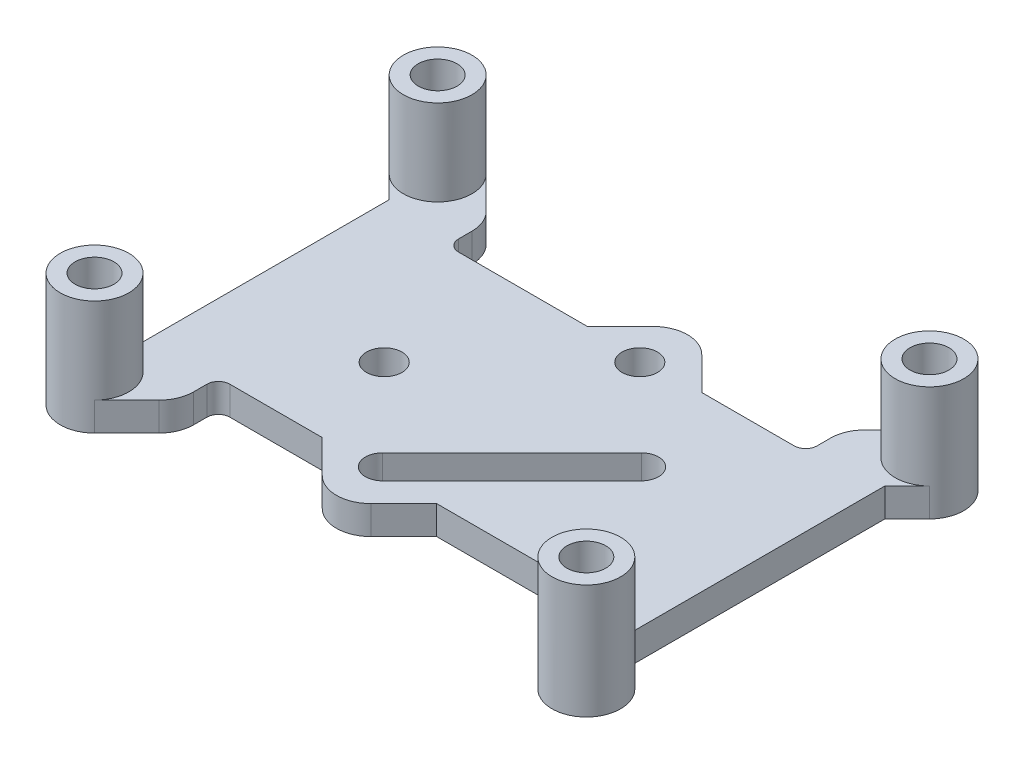
SolidWorks part; units mm, degrees
ref_plane "Front Plane" through (0, 0, 0) normal (0, 0, 1) x (1, 0, 0)
ref_plane "Top Plane" through (0, 0, 0) normal (0, 1, 0) x (1, 0, 0)
ref_plane "Right Plane" through (0, 0, 0) normal (1, 0, 0) x (0, 0, -1)
sketch "Sketch1" plane through (0, 0, 0) normal (0, 1, 0) x (1, 0, 0)
  line L1 (-21.5, 15) -> (21.5, 15) construction
  line L2 (-21.5, 15) -> (-21.5, -15) construction
  line L3 (-21.5, -15) -> (21.5, -15) construction
  line L4 (21.5, 15) -> (21.5, -15) construction
  line L5 (-21.5, 15) -> (21.5, -15) construction
  line L6 (-21.5, -15) -> (21.5, 15) construction
  circle A0 centre (-21.5, 15) radius 1.7
  circle A1 centre (21.5, 15) radius 1.7
  circle A2 centre (21.5, -15) radius 1.7
  circle A3 centre (-21.5, -15) radius 1.7
  circle A4 centre (-21.5, 15) radius 3
  circle A5 centre (-21.5, -15) radius 3
  circle A6 centre (21.5, -15) radius 3
  circle A7 centre (21.5, 15) radius 3
  point P0 (0, 0)
  dimension "D3" = 3.4
  dimension "D4" = 6
  dimension "D1" = 43
  dimension "D2" = 30
extrude "Boss-Extrude1" add sketch "Sketch1" along normal blind 10
sketch "Sketch2" plane through (0, 0, 0) normal (0, 1, 0) x (1, 0, 0)
  line L0 (-21.5, 15) -> (-18.6716, 12.1716) construction
  line L1 (-19.3787, 17.1213) -> (-16.5503, 14.2929)
  line L2 (-23.6213, 12.8787) -> (-21.6716, 10.9289)
  line L3 (-21.5, -15) -> (-18.6716, -12.1716) construction
  line L4 (-23.6213, -12.8787) -> (-21.6716, -10.9289)
  line L5 (-19.3787, -17.1213) -> (-16.5503, -14.2929)
  line L6 (-18.6716, 12.1716) -> (-18.6716, -12.1716) construction
  line L7 (-15.6716, 12.1716) -> (-15.6716, -12.1716)
  line L8 (-21.6716, 10.9289) -> (-21.6716, -10.9289)
  line L9 (0, -1000) -> (0, 49000) construction
  line L10 (18.6716, 12.1716) -> (18.6716, -12.1716) construction
  line L11 (21.5, -15) -> (18.6716, -12.1716) construction
  line L12 (21.5, 15) -> (18.6716, 12.1716) construction
  line L13 (21.6716, 10.9289) -> (21.6716, -10.9289)
  line L14 (15.6716, 12.1716) -> (15.6716, -12.1716)
  line L15 (19.3787, -17.1213) -> (16.5503, -14.2929)
  line L16 (23.6213, -12.8787) -> (21.6716, -10.9289)
  line L17 (23.6213, 12.8787) -> (21.6716, 10.9289)
  line L18 (19.3787, 17.1213) -> (16.5503, 14.2929)
  arc A0 (-19.3787, 17.1213) -> (-23.6213, 12.8787) centre (-21.5, 15) ccw
  circle A2 centre (-21.5, 15) radius 3 construction
  arc A3 (-23.6213, -12.8787) -> (-19.3787, -17.1213) centre (-21.5, -15) ccw
  arc A4 (-16.5503, -14.2929) -> (-15.6716, -12.1716) centre (-18.6716, -12.1716) ccw
  circle A5 centre (-21.5, -15) radius 3 construction
  arc A6 (-15.6716, 12.1716) -> (-16.5503, 14.2929) centre (-18.6716, 12.1716) ccw
  arc A7 (-16.5503, -14.2929) -> (-15.6716, -12.1716) centre (-18.6716, -12.1716) ccw
  arc A8 (-15.6716, 12.1716) -> (-16.5503, 14.2929) centre (-18.6716, 12.1716) ccw
  arc A9 (15.6716, 12.1716) -> (16.5503, 14.2929) centre (18.6716, 12.1716) cw
  arc A10 (16.5503, -14.2929) -> (15.6716, -12.1716) centre (18.6716, -12.1716) cw
  arc A11 (15.6716, 12.1716) -> (16.5503, 14.2929) centre (18.6716, 12.1716) cw
  arc A12 (16.5503, -14.2929) -> (15.6716, -12.1716) centre (18.6716, -12.1716) cw
  arc A13 (23.6213, -12.8787) -> (19.3787, -17.1213) centre (21.5, -15) cw
  arc A14 (19.3787, 17.1213) -> (23.6213, 12.8787) centre (21.5, 15) cw
  point P2 (-20.0858, 13.5858)
  point P13 (-20.0858, -13.5858)
  point P20 (-18.6716, 0)
  point P41 (18.6716, 0)
  point P42 (20.0858, -13.5858)
  point P43 (20.0858, 13.5858)
  dimension "D1" = 45
  dimension "D2" = 45
  dimension "D3" = 4
  dimension "D4" = 4
  dimension "D5" = 3
  dimension "D6" = 3
extrude "Boss-Extrude2" add sketch "Sketch2" along normal blind 2.5 contours L7 A6 L1 A0 L2 L8 L4 A3 L5 A4 | A14 L18 A9 L14 A10 L15 A13 L16 L13 L17 region at (-19.3328, 0, 0) region at (19.3328, 0, 0)
extrude "Cut-Extrude1" cut sketch "Sketch1<2>" against normal through all both and the other way through all contours A3 | A0 | A1 | A2 region at (-21.5, 0, -15) region at (21.5, 0, -15) region at (21.5, 0, 15) region at (-21.5, 0, 15)
sketch "Sketch1<2>" plane through (0, 0, 0) normal (0, 1, 0) x (1, 0, 0) same geometry as "Sketch1"
sketch "Sketch4" plane through (0, 0, 0) normal (0, 1, 0) x (1, 0, 0)
  line L0 (15.6716, 12.1716) -> (15.6716, -12.1716) construction
  line L1 (-15.6716, 10) -> (15.6716, 10)
  line L2 (-15.6716, 10) -> (-15.6716, -10)
  line L3 (-15.6716, -10) -> (15.6716, -10)
  line L4 (15.6716, 10) -> (15.6716, -10)
  line L5 (-15.6716, 10) -> (15.6716, -10) construction
  line L6 (-15.6716, -10) -> (15.6716, 10) construction
  point P0 (0, 0)
  dimension "D1" = 20
extrude "Boss-Extrude3" add sketch "Sketch4" along normal up to surface (2.5 mm away) up to face at (-18.9122, 2.5, 0)
fillet "Fillet2" radius 1 4 edges at (-15.6716, 1.25, -10) (15.6716, 1.25, -10) (15.6716, 1.25, 10) (-15.6716, 1.25, 10)
sketch "Sketch5" plane through (0, 0, 0) normal (0, -1, 0) x (1, 0, 0)
  line L0 (0, 0) -> (34595.1976, 34595.1976) construction
  line L1 (-12.9754, 1.591) -> (-1.591, 12.9754) construction
  line L2 (-12.9754, 1.591) -> (1.591, -12.9754) construction
  line L3 (-1.591, 12.9754) -> (12.9754, -1.591) construction
  line L4 (1.591, -12.9754) -> (12.9754, -1.591) construction
  line L5 (-12.9754, 1.591) -> (12.9754, -1.591) construction
  line L6 (-1.591, 12.9754) -> (1.591, -12.9754) construction
  line L7 (-14.6716, 10) -> (14.6716, 10) construction
  line L8 (-15.8831, 7.8928) -> (1.4159, -9.4062) construction
  line L9 (-1.7324, 9.5813) -> (9.5813, -1.7324) construction
  line L10 (-0.6718, 10.642) -> (10.642, -0.6718)
  line L11 (-2.7931, 8.5206) -> (8.5206, -2.7931)
  circle A0 centre (-9.5813, 1.591) radius 1.55
  circle A1 centre (1.591, -9.5813) radius 1.55
  arc A2 (-0.6718, 10.642) -> (-2.7931, 8.5206) centre (-1.7324, 9.5813) ccw
  arc A3 (8.5206, -2.7931) -> (10.642, -0.6718) centre (9.5813, -1.7324) ccw
  point P4 (0, 0)
  point P16 (3.9244, 3.9244)
  point P23 (0, 0)
  dimension "D4" = 15.8
  dimension "D5" = 7.9
  dimension "D6" = 3.1
  dimension "D7" = 1.5
  dimension "D8" = 2.4
  dimension "D1" = 45
  dimension "D2" = 20.6
  dimension "D3" = 16.1
  dimension "D9" = 16
  dimension "D10" = 1
sketch "Sketch6" plane through (0, 0, 0) normal (0, -1, 0) x (1, 0, 0)
  line L4 (1.591, -4.1626) -> (-3.8277, -9.5813)
  line L5 (1.591, -4.1626) -> (7.0097, -9.5813)
  line L6 (-14.6716, 10) -> (14.6716, 10) construction
  line L10 (-3.8277, -9.5813) -> (1.591, -15)
  line L11 (7.0097, -9.5813) -> (1.591, -15)
  line L12 (1.591, -4.1626) -> (1.591, -15) construction
  line L13 (-3.8277, -9.5813) -> (7.0097, -9.5813) construction
  line L14 (-141421.3562, -141421.3562) -> (176016.5538, 176016.5538) construction
  line L15 (14.6716, -10) -> (-14.6716, -10) construction
  line L16 (-1.591, 15) -> (-9.4453, 7.1457)
  line L17 (-1.591, 15) -> (6.2633, 7.1457)
  line L18 (-9.4453, 7.1457) -> (-1.591, -0.7086)
  line L19 (6.2633, 7.1457) -> (-1.591, -0.7086)
  line L20 (-3.6026, 12.9884) -> (-2.5903, 11.9761) construction
  line L21 (-12.9754, 1.591) -> (-1.591, 12.9754) construction
  line L23 (-1.591, 12.9754) -> (12.9754, -1.591) construction
  line L24 (0.7875, 10.5969) -> (1.7998, 11.6092) construction
  point P1 (1.591, -9.5813)
  dimension "D1" = 5
  dimension "D2" = 5
extrude "Boss-Extrude4" add sketch "Sketch6" against normal up to surface (2.5 mm away) up to face at (0, 2.5, 0)
extrude "Cut-Extrude3" cut sketch "Sketch5" against normal through all both and the other way through all
fillet "Fillet3" radius 3 2 edges at (1.591, 1.25, -15) (-1.591, 1.25, 15)
